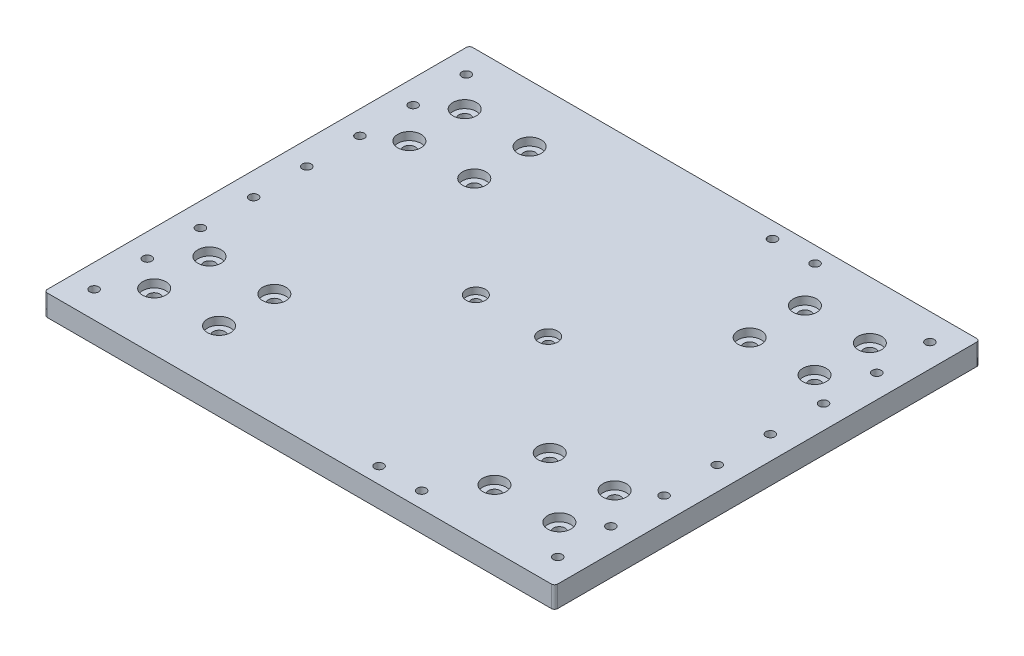
SolidWorks part; units mm, degrees
ref_plane "Front Plane" through (0, 0, 0) normal (0, 0, 1) x (1, 0, 0)
ref_plane "Top Plane" through (0, 0, 0) normal (0, 1, 0) x (1, 0, 0)
ref_plane "Right Plane" through (0, 0, 0) normal (1, 0, 0) x (0, 0, -1)
sketch "Sketch1" plane through (0, 0, 0) normal (0, 1, 0) x (1, 0, 0)
  line L1 (-120, -100) -> (120, -100)
  line L2 (-120, -100) -> (-120, 100)
  line L3 (-120, 100) -> (120, 100)
  line L4 (120, -100) -> (120, 100)
  line L5 (-120, -100) -> (120, 100) construction
  line L6 (-120, 100) -> (120, -100) construction
  point P0 (0, 0)
  dimension "D1" = 240
  dimension "D2" = 200
extrude "Boss-Extrude1" add sketch "Sketch1" along normal mid plane 10
hole_wizard "CBORE for M5 Pan Head Machine Screw1" positions "Sketch11" profile "Sketch10" counterbore size "M5" standard "ANSI Metric" end condition through all
sketch "Sketch11" plane through (66.9231, 5, -81.9693) normal (0, -1, 0) x (-1, 0, 0)
  line L0 (146.9231, -1018.8886) -> (146.9231, 48981.1114) construction
  line L1 (-912.3245, -141.9693) -> (49087.6755, -141.9693) construction
  line L2 (186.9231, 18.0307) -> (186.9231, -181.9693) construction
  line L3 (186.9231, -181.9693) -> (-53.0769, -181.9693) construction
  line L5 (162.1731, -128.9693) -> (131.6731, -128.9693) construction
  line L6 (162.1731, -128.9693) -> (162.1731, -154.9693) construction
  line L7 (162.1731, -154.9693) -> (131.6731, -154.9693) construction
  line L8 (131.6731, -128.9693) -> (131.6731, -154.9693) construction
  line L9 (162.1731, -128.9693) -> (131.6731, -154.9693) construction
  line L10 (162.1731, -154.9693) -> (131.6731, -128.9693) construction
  point P0 (162.1731, -154.9693)
  point P2 (131.6731, -154.9693)
  point P4 (131.6731, -128.9693)
  point P6 (162.1731, -128.9693)
  dimension "D1" = 40
  dimension "D2" = 40
  dimension "D3" = 15.25
  dimension "D4" = 26
  dimension "D5" = 13
  dimension "D6" = 30.5
sketch "Sketch10" plane through (-95.25, 5, 73) normal (1, 0, 0) x (0, 0, 1)
  line L0 (0, 0) -> (0, 10)
  line L1 (0, 10) -> (2.75, 10)
  line L3 (2.75, 10) -> (2.75, 3.7)
  line L4 (2.75, 3.7) -> (5.5, 3.7)
  line L5 (5.5, 3.7) -> (5.5, 0)
  line L7 (5.5, 0) -> (0, 0)
  line L11 (0, -6.35) -> (0, 107.95) construction
  dimension "Thru Hole Dia." = 5.5
  dimension "Thru Hole Depth" = 10
  dimension "C'Bore Dia." = 11
  dimension "C'Bore Depth" = 3.7
mirror "Mirror1" about plane through (0, 0, 0) normal (1, 0, 0) of "CBORE for M5 Pan Head Machine Screw1"
mirror "Mirror2" about plane through (0, 0, 0) normal (0, 0, 1) of "Mirror1"
hole_wizard "CBORE for M4 Pan Head Machine Screw1" positions "Sketch9" profile "Sketch8" counterbore size "M4" standard "ANSI Metric" end condition through all
sketch "Sketch9" plane through (-30.3385, 5, -23.5385) normal (0, -1, 0) x (-1, 0, 0)
  line L0 (-1000, -23.5385) -> (49000, -23.5385) construction
  point P0 (-13.3385, -23.5385)
  point P2 (-47.3385, -23.5385)
  dimension "D1" = 17
  dimension "D2" = 17
sketch "Sketch8" plane through (-17, 5, 0) normal (1, 0, 0) x (0, 0, 1)
  line L0 (0, 0) -> (0, 10)
  line L1 (0, 10) -> (2.25, 10)
  line L3 (2.25, 10) -> (2.25, 3.1)
  line L4 (2.25, 3.1) -> (4.5, 3.1)
  line L5 (4.5, 3.1) -> (4.5, 0)
  line L7 (4.5, 0) -> (0, 0)
  line L11 (0, -6.35) -> (0, 107.95) construction
  dimension "Thru Hole Dia." = 4.5
  dimension "Thru Hole Depth" = 10
  dimension "C'Bore Dia." = 9
  dimension "C'Bore Depth" = 3.1
hole_wizard "M5x0.8 Tapped Hole1" positions "Sketch7" profile "Sketch5" tap size "M5x0.8" standard "ANSI Metric" end condition through all
sketch "Sketch7" plane through (0, 5, 0) normal (0, 1, 0) x (1, 0, 0)
  line L0 (120, 100) -> (-120, 100) construction
  line L1 (-120, 100) -> (-120, -100) construction
  line L2 (120, -100) -> (120, 100) construction
  point P0 (-109, 87.5)
  point P2 (109, 87.5)
  dimension "D1" = 12.5
  dimension "D2" = 11
  dimension "D3" = 11
  dimension "D4" = 12.5
sketch "Sketch5" plane through (-109, 5, -87.5) normal (1, 0, 0) x (0, 0, 1)
  line L0 (0, 0) -> (0, 10)
  line L1 (0, 10) -> (2.1, 10)
  line L2 (2.1, 10) -> (2.1, 0)
  line L5 (2.1, 0) -> (0, 0)
  line L11 (0, -6.35) -> (0, 107.95) construction
  dimension "Thru Tap Drill Dia." = 4.2
  dimension "Thru Tap Drill Depth" = 10
cosmetic thread "Hole Thread1" parameters "D2"=5
cosmetic thread "Hole Thread2" parameters "D2"=5
fillet "Fillet1" radius 1.5 4 edges at (-120, 0, -100) (120, 0, -100) (-120, 0, 100) (120, 0, 100)
pattern_linear "LPattern2" count 8 spacing 25 along (0, 0, 1) of "M5x0.8 Tapped Hole1"
hole_wizard "M5x0.8 Tapped Hole2" positions "Sketch13" profile "Sketch12" tap size "M5x0.8" standard "ANSI Metric" end condition through all
sketch "Sketch13" plane through (0, 5, 0) normal (0, 1, 0) x (1, 0, 0)
  line L0 (118.5, 100) -> (-118.5, 100) construction
  point P0 (30, 92.5)
  point P2 (50, 92.5)
  dimension "D1" = 50
  dimension "D2" = 20
  dimension "D3" = 7.5
  dimension "D4" = 7.5
sketch "Sketch12" plane through (30, 5, -92.5) normal (1, 0, 0) x (0, 0, 1)
  line L0 (0, 0) -> (0, 10)
  line L1 (0, 10) -> (2.1, 10)
  line L2 (2.1, 10) -> (2.1, 0)
  line L5 (2.1, 0) -> (0, 0)
  line L11 (0, -6.35) -> (0, 107.95) construction
  dimension "Thru Tap Drill Dia." = 4.2
  dimension "Thru Tap Drill Depth" = 10
cosmetic thread "Hole Thread3" parameters "D2"=5
cosmetic thread "Hole Thread4" parameters "D2"=5
mirror "Mirror3" about plane through (0, 0, 0) normal (0, 0, 1) of "M5x0.8 Tapped Hole2"
